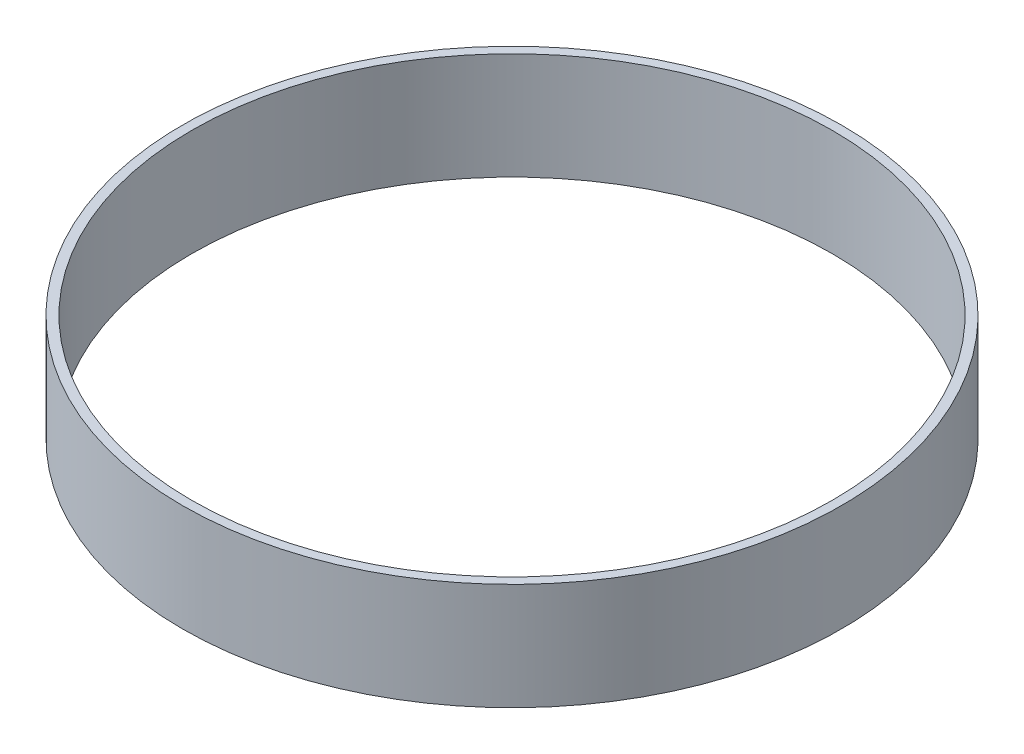
SolidWorks part; units mm, degrees
material "A-Glass Fiber"
ref_plane "Front Plane" through (0, 0, 0) normal (0, 0, 1) x (1, 0, 0)
ref_plane "Top Plane" through (0, 0, 0) normal (0, 1, 0) x (1, 0, 0)
ref_plane "Right Plane" through (0, 0, 0) normal (1, 0, 0) x (0, 0, -1)
sketch "Sketch1" plane through (0, 0, 0) normal (0, 1, 0) x (1, 0, 0)
  circle A0 centre (0, 0) radius 76.1746
  circle A1 centre (0, 0) radius 78.359
  dimension "D1" = 152.3492
  dimension "D2" = 156.718
extrude "Boss-Extrude1" add sketch "Sketch1" along normal blind 25.4
equation "\"Mid_Tube_Length\"= 1in"
equation "\"D1@Boss-Extrude1\"=\"Mid_Tube_Length\""
equation "\"Bodytube_OD\"= 6.17in"
equation "\"Bodytube_ID\"= 5.998in"
equation "\"D1@Sketch1\"=\"Bodytube_ID\""
equation "\"D2@Sketch1\"=\"Bodytube_OD\""
